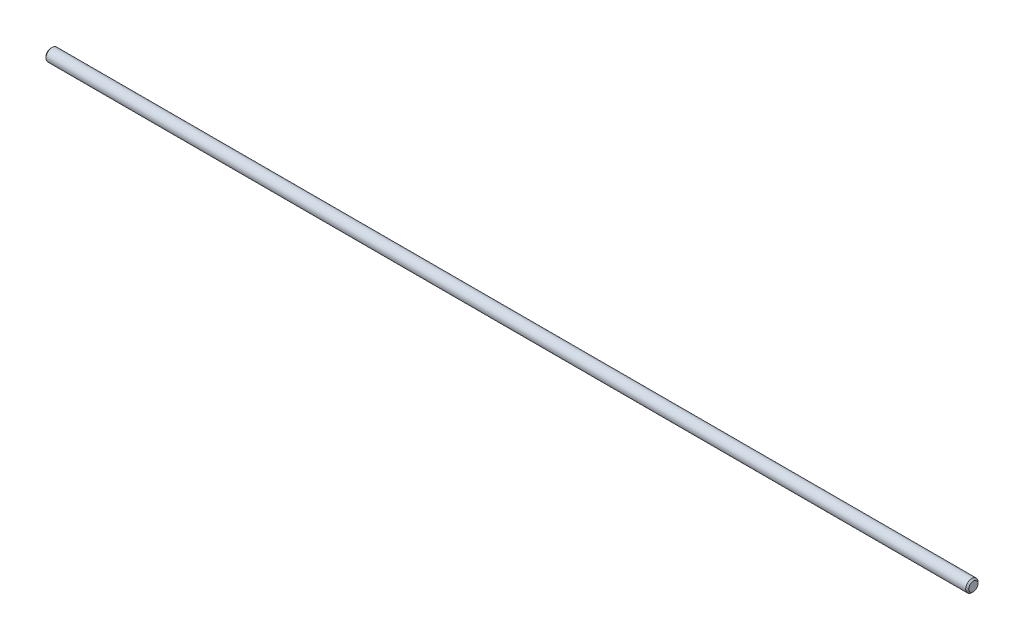
SolidWorks part; units mm, degrees
ref_plane "Front Plane" through (0, 0, 0) normal (0, 0, 1) x (1, 0, 0)
ref_plane "Top Plane" through (0, 0, 0) normal (0, 1, 0) x (1, 0, 0)
ref_plane "Right Plane" through (0, 0, 0) normal (1, 0, 0) x (0, 0, -1)
sketch "Sketch1" plane through (0, 0, 0) normal (0, 0, 1) x (1, 0, 0)
  line L0 (-75, 0) -> (75, 0) construction
  line L1 (75, 1) -> (75, -1) construction
  line L2 (-75, 1) -> (-75, -1) construction
  point P6 (73.6, -1)
  dimension "D1" = 1.4
  dimension "Thread Diameter" = 2
  dimension "Length" = 150
sketch "Sketch2" plane through (0, 0, 0) normal (1, 0, 0) x (0, 0, -1)
  circle A0 centre (0, 0) radius 1
extrude "Boss-Extrude1" add sketch "Sketch2" against normal up to vertex (75 mm away) and the other way up to vertex (75 mm away) up to point (-75, 0, 0) other way up to point (75, 0, 0)
sketch "Sketch3" plane through (75, 0, 0) normal (1, 0, 0) x (0, 0, -1)
  circle A1 centre (0, 0) radius 1
  circle A2 centre (0, 0) radius 1
  dimension "D1" = 0
curve "Helix/Spiral1" pitch 0.4 height 101 turns 252.5
sketch "Sketch4" plane through (0, 0, 0) normal (0, 0, 1) x (1, 0, 0)
  line L1 (74.9714, 1.0495) -> (75.3714, 1.0495) construction
  line L2 (74.9714, 1.0495) -> (75.1714, 0.7031) construction
  line L3 (75.1714, 0.7031) -> (75.3714, 1.0495) construction
  line L4 (75.1714, 1.0495) -> (75.1714, 1) construction
  line L5 (75.1714, 0.7031) -> (75.1714, 0.7526) construction
  line L6 (75.1429, 0.7526) -> (75.2, 0.7526) construction
  line L7 (75, 1) -> (75.3429, 1) construction
  line L8 (75, 1) -> (75.1429, 0.7526)
  line L9 (75.1429, 0.7526) -> (75.2, 0.7526)
  line L10 (75.2, 0.7526) -> (75.3429, 1)
  line L11 (75.3429, 1) -> (75, 1)
  dimension "Pitch" = 0.4
  dimension "D2" = 0.0571
sketch "Sketch5" plane through (75, 0, 0) normal (1, 0, 0) x (0, 0, -1)
  circle A0 centre (0, 0) radius 0.7526
extrude "Cut-Extrude1" cut sketch "Sketch5" against normal through all draft 45 flip side to cut
mirror "Mirror1" about plane through (0, 0, 0) normal (1, 0, 0) of "Cut-Extrude1"
equation "\"D2@Sketch4\" = \"Pitch@Sketch4\"/7"
